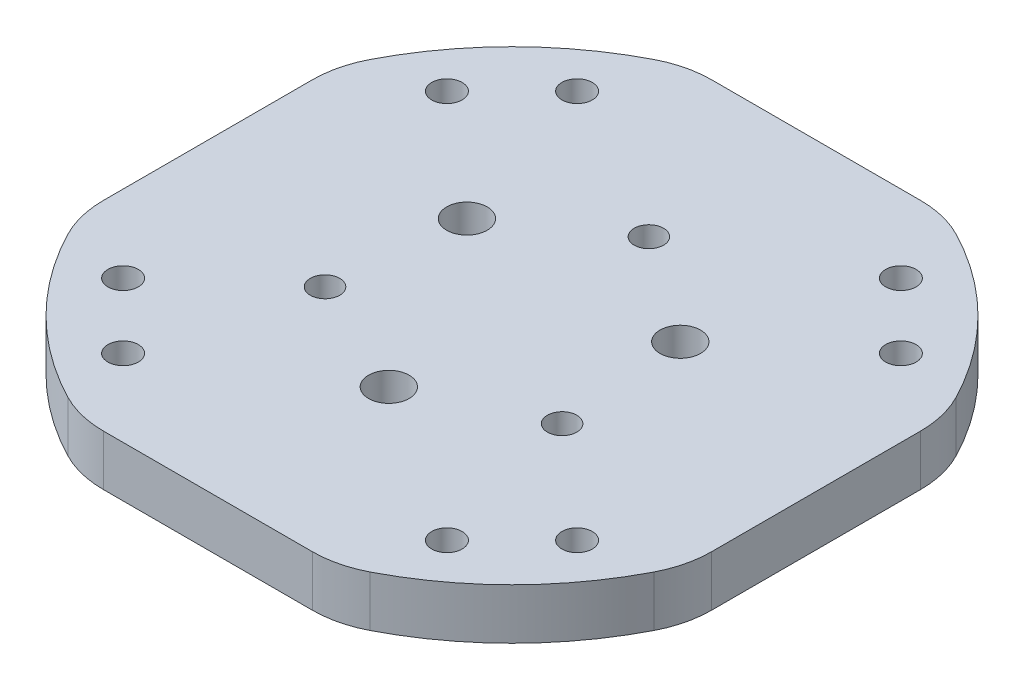
SolidWorks part; units mm, degrees
material "6061 合金"
ref_plane "前视基准面" through (0, 0, 0) normal (0, 0, 1) x (1, 0, 0)
ref_plane "上视基准面" through (0, 0, 0) normal (0, 1, 0) x (1, 0, 0)
ref_plane "右视基准面" through (0, 0, 0) normal (1, 0, 0) x (0, 0, -1)
sketch "草图1" plane through (0, 0, 0) normal (0, 1, 0) x (1, 0, 0)
  line L0 (0, 0) -> (0, 33.3478) construction
  line L1 (0, 0) -> (11.2563, 0) construction
  line L2 (-11.6913, -6.75) -> (0, 0) construction
  line L3 (0, 0) -> (11.6913, -6.75) construction
  line L4 (0, 0) -> (-10.5222, 6.075) construction
  line L5 (10.5222, 6.075) -> (0, 0) construction
  circle A0 centre (0, 0) radius 19
  circle A1 centre (0, 13.5) radius 1.45
  circle A2 centre (0, 0) radius 13.5 construction
  circle A3 centre (-11.6913, -6.75) radius 1.45
  circle A4 centre (11.6913, -6.75) radius 1.45
  circle A5 centre (0, 0) radius 12.15 construction
  circle A6 centre (-10.5222, 6.075) radius 2
  circle A7 centre (0, -12.15) radius 2
  circle A8 centre (10.5222, 6.075) radius 2
  dimension "D1" = 38
  dimension "D2" = 27
  dimension "D3" = 2.9
  dimension "D6" = 24.3
  dimension "D8" = 4
  dimension "D4" = 120
  dimension "D5" = 120
  dimension "D7" = 60
  dimension "D9" = 60
extrude "凸台-拉伸1" add sketch "草图1" along normal blind 12
sketch "草图2" plane through (0, 12, 0) normal (0, 1, 0) x (1, 0, 0)
  line L0 (0, 21.9393) -> (0, 0) construction
  line L1 (0, 21.9393) -> (-19, 10.9697)
  line L2 (-19, 10.9697) -> (-19, -10.9697)
  line L3 (-19, -10.9697) -> (0, -21.9393)
  line L4 (0, -21.9393) -> (19, -10.9697)
  line L5 (19, -10.9697) -> (19, 10.9697)
  line L6 (19, 10.9697) -> (0, 21.9393)
  circle A0 centre (0, 0) radius 19 construction
  circle A1 centre (0, 13.5) radius 1.45
  circle A2 centre (0, 13.5) radius 1.45 construction
  circle A3 centre (-10.5222, 6.075) radius 2
  circle A4 centre (-10.5222, 6.075) radius 2 construction
  circle A5 centre (10.5222, 6.075) radius 2
  circle A6 centre (10.5222, 6.075) radius 2 construction
  circle A7 centre (-11.6913, -6.75) radius 1.45
  circle A8 centre (-11.6913, -6.75) radius 1.45 construction
  circle A9 centre (0, -12.15) radius 2
  circle A10 centre (0, -12.15) radius 2 construction
  circle A11 centre (11.6913, -6.75) radius 1.45
  circle A12 centre (11.6913, -6.75) radius 1.45 construction
  dimension "D1" = 38
extrude "凸台-拉伸2" add sketch "草图2" against normal blind 7
sketch "草图3" plane through (9.5, 0, 16.4545) normal (0.5, 0, 0.866) x (0.866, 0, -0.5)
  line L1 (0, 12) -> (0, 5) construction
  line L2 (-10.9697, 12) -> (10.9697, 12) construction
  circle A1 centre (0, 8.5) radius 1.45
  dimension "D1" = 2.9
extrude "切除-拉伸1" cut sketch "草图3" against normal blind 8
sketch "草图4" plane through (-9.5, 0, 16.4545) normal (-0.5, 0, 0.866) x (0.866, 0, 0.5)
  line L0 (0, 5) -> (0, 12) construction
  line L1 (-10.9697, 12) -> (10.9697, 12) construction
  circle A0 centre (0, 8.5) radius 1.45
  dimension "D1" = 2.9
extrude "切除-拉伸2" cut sketch "草图4" against normal blind 8
sketch "草图5" plane through (-19, 0, 0) normal (-1, 0, 0) x (0, 0, 1)
  line L0 (0, 5) -> (0, 12) construction
  line L1 (-10.9697, 12) -> (10.9697, 12) construction
  circle A0 centre (0, 8.5) radius 1.45
  dimension "D1" = 2.9
extrude "切除-拉伸3" cut sketch "草图5" against normal blind 8
sketch "草图6" plane through (19, 0, 0) normal (1, 0, 0) x (0, 0, -1)
  line L0 (0, 12) -> (0, 5) construction
  line L1 (-10.9697, 12) -> (10.9697, 12) construction
  circle A0 centre (0, 8.5) radius 1.45
  dimension "D1" = 2.9
extrude "切除-拉伸4" cut sketch "草图6" against normal blind 8
sketch "草图7" plane through (9.5, 0, -16.4545) normal (0.5, 0, -0.866) x (-0.866, 0, -0.5)
  line L0 (0, 12) -> (0, 5) construction
  line L1 (-10.9697, 12) -> (10.9697, 12) construction
  circle A0 centre (0, 8.5) radius 1.45
  dimension "D1" = 2.9
extrude "切除-拉伸5" cut sketch "草图7" against normal blind 8
sketch "草图8" plane through (0, 12, 0) normal (0, 1, 0) x (1, 0, 0)
  line L0 (0, 0) -> (0, 38.6602) construction
  line L1 (0, 0) -> (44.9682, 0) construction
  line L2 (0, 0) -> (-22.3882, 15.9693) construction
  line L3 (0, 0) -> (-15.9693, 22.3882) construction
  line L4 (10.3078, 30) -> (-10.3078, 30)
  line L5 (-30, 30) -> (30, 30) construction
  line L6 (-30, 30) -> (-30, -30) construction
  line L7 (-30, -30) -> (30, -30) construction
  line L8 (30, 30) -> (30, -30) construction
  line L9 (-30, 30) -> (30, -30) construction
  line L10 (-30, -30) -> (30, 30) construction
  line L11 (-30, -10.3078) -> (-30, 10.3078)
  line L12 (30, -10.3078) -> (30, 10.3078)
  line L13 (10.3078, -30) -> (-10.3078, -30)
  circle A0 centre (0, 0) radius 32.5 construction
  circle A1 centre (0, 0) radius 27.5 construction
  circle A2 centre (-22.3882, 15.9693) radius 1.5
  circle A3 centre (-15.9693, 22.3882) radius 1.5
  circle A4 centre (-22.3882, -15.9693) radius 1.5
  circle A5 centre (-15.9693, -22.3882) radius 1.5
  circle A6 centre (15.9693, -22.3882) radius 1.5
  circle A7 centre (22.3882, -15.9693) radius 1.5
  circle A8 centre (22.3882, 15.9693) radius 1.5
  circle A9 centre (15.9693, 22.3882) radius 1.5
  arc A10 (-14.889, 28.8889) -> (-28.8889, 14.889) centre (0, 0) ccw
  arc A11 (14.889, 28.8889) -> (28.8889, 14.889) centre (0, 0) cw
  arc A12 (14.889, -28.8889) -> (28.8889, -14.889) centre (0, 0) ccw
  arc A13 (-14.889, -28.8889) -> (-28.8889, -14.889) centre (0, 0) cw
  arc A14 (-10.3078, -30) -> (-14.889, -28.8889) centre (-10.3078, -20) cw
  arc A15 (-28.8889, -14.889) -> (-30, -10.3078) centre (-20, -10.3078) cw
  arc A16 (-30, 10.3078) -> (-28.8889, 14.889) centre (-20, 10.3078) cw
  arc A17 (-14.889, 28.8889) -> (-10.3078, 30) centre (-10.3078, 20) cw
  arc A18 (14.889, 28.8889) -> (10.3078, 30) centre (10.3078, 20) ccw
  arc A19 (28.8889, 14.889) -> (30, 10.3078) centre (20, 10.3078) cw
  arc A20 (28.8889, -14.889) -> (30, -10.3078) centre (20, -10.3078) ccw
  arc A21 (14.889, -28.8889) -> (10.3078, -30) centre (10.3078, -20) cw
  circle A22 centre (0, 13.5) radius 1.5
  circle A23 centre (11.6913, -6.75) radius 1.5
  circle A24 centre (0, -12.15) radius 2
  circle A25 centre (10.5222, 6.075) radius 2
  circle A26 centre (-11.6913, -6.75) radius 1.5
  circle A27 centre (-10.5222, 6.075) radius 2
  circle A28 centre (-10.5222, 6.075) radius 2 construction
  circle A29 centre (10.5222, 6.075) radius 2 construction
  point P34 (0, 30)
  point P37 (30, 0)
  point P40 (-30, 0)
  point P42 (-12.5, -30)
  point P45 (-30, -12.5)
  point P48 (-30, 12.5)
  point P51 (-12.5, 30)
  point P54 (12.5, 30)
  point P57 (30, 12.5)
  point P60 (30, -12.5)
  point P63 (12.5, -30)
  dimension "D1" = 65
  dimension "D2" = 55
  dimension "D5" = 3
  dimension "D7" = 10
  dimension "D8" = 10
  dimension "D9" = 3
  dimension "D3" = 35.5
  dimension "D4" = 35.5
  dimension "D6" = 60
extrude "凸台-拉伸3" add sketch "草图8" against normal blind 5
fillet "圆角1" radius 3 6 edges at (-9.5, 7, 16.4545) (9.5, 7, 16.4545) (19, 7, 0) (9.5, 7, -16.4545) (-9.5, 7, -16.4545) (-19, 7, 0)
chamfer "倒角1" distance 1.55 angle 45 8 edges at (22.3882, 7, -17.4693) (15.9693, 7, -23.8882) (-15.9693, 7, -20.8882) (-22.3882, 7, -14.4693) (22.3882, 7, 17.4693) (15.9693, 7, 23.8882) (-15.9693, 7, 20.8882) (-22.3882, 7, 14.4693)
